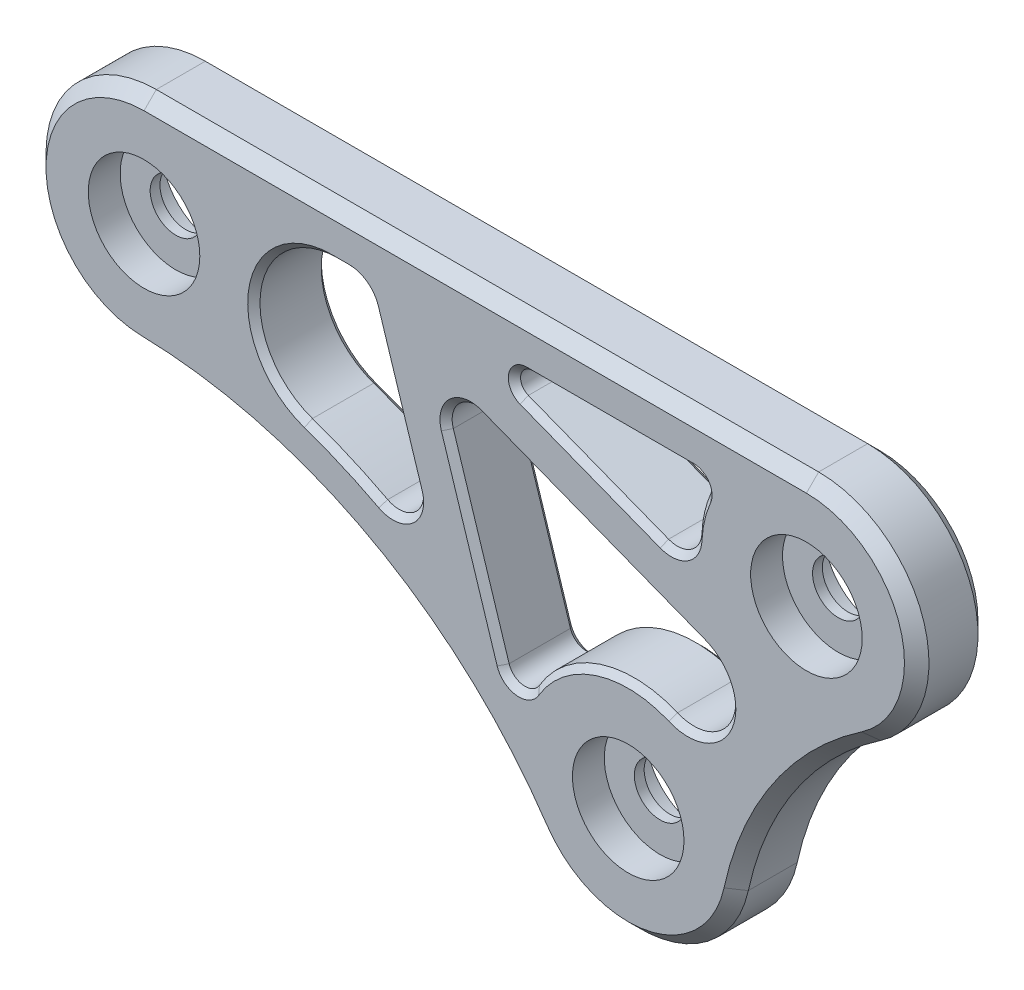
SolidWorks part; units mm, degrees
ref_plane "Front Plane" through (0, 0, 0) normal (0, 0, 1) x (1, 0, 0)
ref_plane "Top Plane" through (0, 0, 0) normal (0, 1, 0) x (1, 0, 0)
ref_plane "Right Plane" through (0, 0, 0) normal (1, 0, 0) x (0, 0, -1)
sketch "Sketch1" plane through (0, 0, 0) normal (0, 0, 1) x (1, 0, 0)
  line L0 (0, 0) -> (14.539, 21.555) construction
  line L1 (14.539, 21.555) -> (-39.5017, 21.555) construction
  line L2 (-39.5017, 21.555) -> (0, 0) construction
  line L3 (-39.5017, 30.555) -> (14.539, 30.555)
  circle A0 centre (0, 0) radius 2.1
  circle A1 centre (-39.5017, 21.555) radius 2.1
  circle A2 centre (14.539, 21.555) radius 2.1
  arc A3 (-39.5017, 30.555) -> (-39.7036, 12.5572) centre (-39.5017, 21.555) ccw
  arc A4 (-7.4573, -5.0387) -> (8.7969, -1.9013) centre (0, 0) ccw
  arc A5 (19.5973, 14.1109) -> (14.539, 30.555) centre (14.539, 21.555) ccw
  arc A6 (8.7969, -1.9013) -> (19.5973, 14.1109) centre (34.21, -7.3941) cw
  arc A7 (-39.7036, 12.5572) -> (-7.4573, -5.0387) centre (-40.6011, -27.4327) cw
  dimension "D4" = 4.2
  dimension "D5" = 18
  dimension "D6" = 40
  dimension "D7" = 26
  dimension "D1" = 45
  dimension "D2" = 26
  dimension "D3" = 56
extrude "Boss-Extrude1" add sketch "Sketch1" along normal blind 3 and the other way blind 3
sketch "Sketch2" plane through (0, 0, 3) normal (0, 0, 1) x (1, 0, 0)
  circle A0 centre (-39.5017, 21.555) radius 4.55
  circle A1 centre (14.539, 21.555) radius 4.55
  circle A2 centre (0, 0) radius 4.55
  dimension "D1" = 9.1
extrude "Cut-Extrude1" cut sketch "Sketch2" against normal blind 2.6
mirror "Mirror1" about plane through (0, 0, 0) normal (0, 0, 1) of "Cut-Extrude1"
chamfer "Chamfer1" distance 1 angle 45 12 edges at (1.7057, -8.8369, -3) (12.6551, 7.1449, -3) (-21.4411, 7.6799, -3) (23.1412, 24.2011, -3) (-48.5011, 21.6559, -3) (-12.4813, 30.555, -3) (1.7057, -8.8369, 3) (12.6551, 7.1449, 3) (-21.4411, 7.6799, 3) (23.1412, 24.2011, 3) (-48.5011, 21.6559, 3) (-12.4813, 30.555, 3)
sketch "Sketch3" plane through (0, 0, 3) normal (0, 0, 1) x (1, 0, 0)
  line L2 (-39.5017, 26.555) -> (14.539, 26.555)
  line L3 (-24.1803, 26.555) -> (-22.7643, 26.555)
  line L4 (-8.6439, 24.6227) -> (2.7958, 20.1832)
  line L6 (-14.7678, 19.2182) -> (-10.2137, 4.8782)
  line L7 (-20.8582, 25.1603) -> (-17.2814, 13.8979)
  line L10 (-8.2821, 26.555) -> (5.3441, 26.555)
  line L12 (-12.1381, 21.6881) -> (6.1012, 14.6098)
  arc A2 (6.2588, 25.1592) -> (5.5174, 21.9584) centre (14.539, 21.555) ccw
  arc A3 (3.5262, 8.2804) -> (-7.7389, 4.5945) centre (0, 0) ccw
  arc A5 (6.2588, 25.1592) -> (5.3441, 26.555) centre (5.3441, 25.5574) ccw
  arc A8 (-24.1803, 26.555) -> (-26.2592, 14.1801) centre (-24.1803, 20.1929) ccw
  arc A9 (-20.1192, 11.5228) -> (-26.2592, 14.1801) centre (-40.615, -27.4121) ccw
  arc A12 (2.7958, 20.1832) -> (5.5174, 21.9584) centre (3.5194, 22.0477) ccw
  arc A13 (-12.1381, 21.6881) -> (-14.7678, 19.2182) centre (-12.8616, 19.8236) ccw
  arc A14 (-17.2814, 13.8979) -> (-20.1192, 11.5228) centre (-19.1876, 13.2926) cw
  arc A15 (-20.8582, 25.1603) -> (-22.7643, 26.555) centre (-22.7643, 24.555) ccw
  arc A16 (-8.6439, 24.6227) -> (-8.2821, 26.555) centre (-8.2821, 25.555) cw
  arc A17 (3.5262, 8.2804) -> (6.1012, 14.6098) centre (4.865, 11.4243) ccw
  arc A18 (-10.2137, 4.8782) -> (-7.7389, 4.5945) centre (-8.9127, 5.2914) ccw
  point P31 (-15.674, 8.8363)
  point P38 (-13.6229, 26.555)
  dimension "D1" = 4
  dimension "D3" = 2
  dimension "D5" = 1
extrude "Cut-Extrude2" cut sketch "Sketch3" against normal through all
chamfer "Chamfer2" distance 0.5 angle 45 36 edges at (6.1785, 26.1042, -3) (-1.469, 26.555, -3) (5.7413, 23.5928, -3) (-9.265, 25.739, -3) (4.6121, 20.3726, -3) (-2.924, 22.403, -3) (6.1785, 26.1042, 3) (-1.469, 26.555, 3) (5.7413, 23.5928, 3) (-9.265, 25.739, 3) (4.6121, 20.3726, 3) (-2.924, 22.403, 3) (-30.4544, 21.2469, -3) (-23.1386, 12.9683, -3) (-23.4723, 26.555, -3) (-17.904, 11.7588, -3) (-21.5834, 26.1691, -3) (-19.0698, 19.5291, -3) (-30.4544, 21.2469, 3) (-23.1386, 12.9683, 3) (-23.4723, 26.555, 3) (-17.904, 11.7588, 3) (-21.5834, 26.1691, 3) (-19.0698, 19.5291, 3) (-14.2308, 21.2814, -3) (-12.4908, 12.0482, -3) (-3.0184, 18.1489, -3) (-9.0681, 3.9352, -3) (8.0301, 10.1366, -3) (-2.7988, 8.5538, -3) (-14.2308, 21.2814, 3) (-12.4908, 12.0482, 3) (-3.0184, 18.1489, 3) (-9.0681, 3.9352, 3) (8.0301, 10.1366, 3) (-2.7988, 8.5538, 3)
